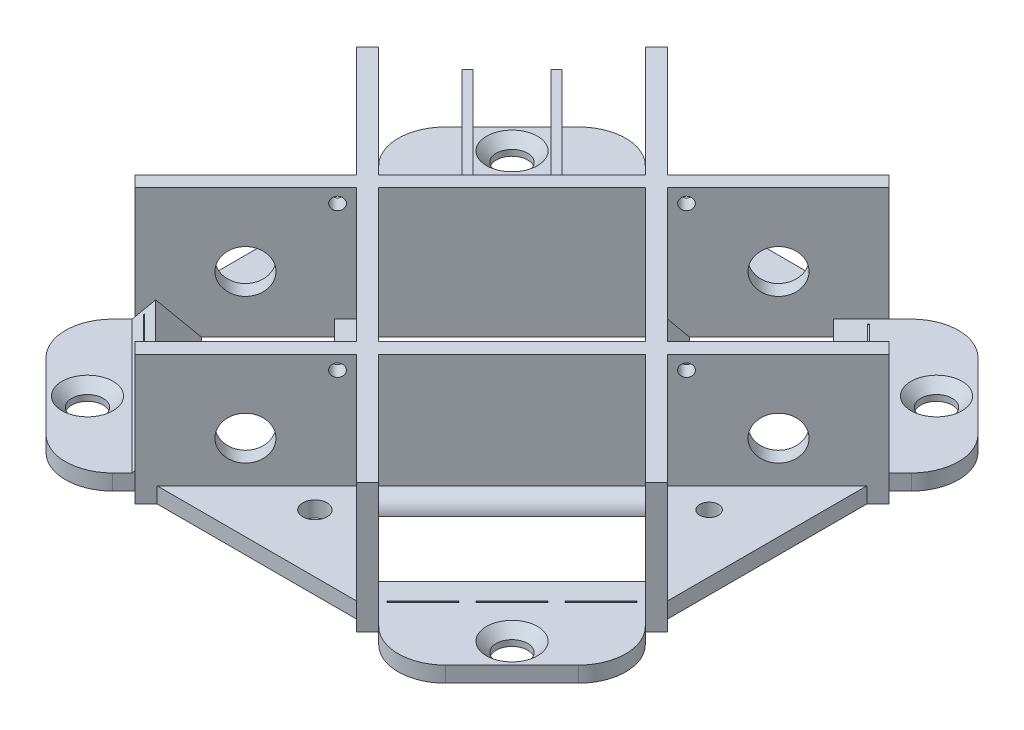
SolidWorks part; units mm, degrees
material "Windform GT"
ref_plane "Front Plane" through (0, 0, 0) normal (0, 0, 1) x (1, 0, 0)
ref_plane "Top Plane" through (0, 0, 0) normal (0, 1, 0) x (1, 0, 0)
ref_plane "Right Plane" through (0, 0, 0) normal (1, 0, 0) x (0, 0, -1)
ref_axis "Axis1" through (0, 2.1, 0) along (0, -1, 0)
sketch "Usable Space" plane through (0, 0, 0) normal (0, 1, 0) x (1, 0, 0)
  line L1 (-32.5, -32.5) -> (32.5, -32.5) construction
  line L2 (-32.5, -32.5) -> (-32.5, 32.5) construction
  line L3 (-32.5, 32.5) -> (32.5, 32.5) construction
  line L4 (32.5, -32.5) -> (32.5, 32.5) construction
  line L5 (-32.5, -32.5) -> (32.5, 32.5) construction
  line L6 (-32.5, 32.5) -> (32.5, -32.5) construction
  point P0 (0, 0)
  dimension "D1" = 65
sketch "Sketch3" plane through (0, 0, 0) normal (0, 1, 0) x (1, 0, 0)
  line L0 (-32.5, -12.701) -> (-12.701, -32.5)
  line L1 (-32.5, -32.5) -> (-32.5, 32.5) construction
  line L2 (-12.701, -32.5) -> (0, -19.799)
  line L3 (-32.5, -32.5) -> (32.5, 32.5) construction
  line L4 (0, -19.799) -> (0, 0)
  line L5 (0, 0) -> (-19.799, 0)
  line L7 (-19.799, 0) -> (-32.5, -12.701)
  line L8 (-32.5, -32.5) -> (32.5, -32.5) construction
  dimension "D1" = 28
extrude "General shape" add sketch "Sketch3" along normal blind 2
sketch "Sketch4" plane through (0, 2, 0) normal (0, 1, 0) x (1, 0, 0)
  line L0 (-19.799, 0) -> (-32.5, -12.701)
  line L1 (-19.799, 0) -> (-32.5, -12.701) construction
  line L2 (-32.5, -12.701) -> (-31.0858, -14.1152)
  line L3 (-31.0858, -14.1152) -> (-16.9706, 0)
  line L4 (0, 0) -> (-19.799, 0) construction
  line L5 (-16.9706, 0) -> (-19.799, 0)
  line L6 (-22.6005, -22.6005) -> (0, 0) construction
  line L7 (-32.5, -12.701) -> (-12.701, -32.5) construction
  line L8 (-14.1152, -31.0858) -> (0, -16.9706)
  line L9 (-12.701, -32.5) -> (-14.1152, -31.0858)
  line L10 (0, -19.799) -> (-12.701, -32.5)
  line L11 (0, -16.9706) -> (0, -19.799)
  dimension "D1" = 2
extrude "Retaining walls" add sketch "Sketch4" along normal blind 14.5
sketch "Sketch14" plane through (0, 0, 0) normal (0, -1, 0) x (1, 0, 0)
  line L0 (-19.799, 0) -> (-32.5, 12.701)
  line L1 (-19.799, 0) -> (-32.5, 12.701) construction
  line L2 (-32.5, 12.701) -> (-32.5, 0)
  line L3 (-32.5, 0) -> (-19.799, 0)
  line L4 (0, 19.799) -> (0, 32.5)
  line L5 (0, 32.5) -> (-12.701, 32.5)
  line L6 (-12.701, 32.5) -> (0, 19.799) construction
  line L7 (0, 19.799) -> (-12.701, 32.5)
  circle A1 centre (-29.049, 0) radius 1 construction
  dimension "D1" = 9.25
  dimension "D2" = 2
extrude "Exterior mounting edge" add sketch "Sketch14" against normal blind 2
sketch "Sketch18" plane through (0, 2, 0) normal (0, 1, 0) x (1, 0, 0)
  line L0 (-16.9706, 0) -> (0, -16.9706)
  line L1 (-18.3848, -1.4142) -> (-1.4142, -18.3848)
  line L2 (-31.0858, -14.1152) -> (-16.9706, 0) construction
  line L3 (0, -16.9706) -> (-14.1152, -31.0858) construction
  line L4 (-18.3848, -1.4142) -> (-16.9706, 0)
  line L5 (0, -16.9706) -> (-1.4142, -18.3848)
  dimension "D1" = 2
extrude "Rear wall" add sketch "Sketch18" along normal blind 14.5
sketch "Sketch19" plane through (-8.4853, 0, 8.4853) normal (0.7071, 0, -0.7071) x (-0.7071, 0, -0.7071)
  line L0 (0, 16.5) -> (0, 2) construction
  line L1 (-12, 16.5) -> (12, 16.5) construction
  line L2 (-12, 2) -> (12, 2) construction
  point P6 (0, 9.25)
fillet "Fillet13" [suppressed] radius 1
ref_plane "Plane2" [suppressed] through (0, 0, 0) normal (0.7071, 0, 0.7071) x (0.7071, 0, -0.7071)
sketch "Sketch35" plane through (-9.8995, 0, -9.8995) normal (-0.7071, 0, -0.7071) x (-0.7071, 0, 0.7071)
  line L0 (24, 16.5) -> (24, 2) construction
  line L2 (14, 16.5) -> (14, 2) construction
  line L3 (14, 2) -> (31.9619, 2) construction
  line L4 (15.7119, 16.5) -> (15.7119, 2) construction
  line L5 (14, 16.5) -> (31.9619, 16.5) construction
  line L6 (14, 2) -> (31.9619, 2) construction
  line L7 (14, 16.5) -> (31.9619, 16.5) construction
  line L8 (31.9619, 16.5) -> (31.9619, 2) construction
  circle A0 centre (24, 7.25) radius 2.75
  circle A1 centre (15.7119, 14.75) radius 0.8
  dimension "D1" = 5.5
  dimension "D4" = 1.6
  dimension "D5" = 1.75
  dimension "D6" = 9.25
  dimension "D2" = 10
  dimension "D3" = 16.25
extrude "Cut-Extrude2" cut sketch "Sketch35" against normal through all both and the other way through all
pattern_circular "CirPattern2" count 4 over 360 about axis through (0, 2.1, 0) along (0, -1, 0) of "General shape", "Retaining walls"
combine bodies "Combine1" operation type add bodies to combine 104 111 110 139
sketch "Exterior mounting hole location" plane through (0, 2, 0) normal (0, 1, 0) x (1, 0, 0)
  line L0 (-32.5, 0) -> (-19.799, 0) construction
  line L1 (-32.5, -12.701) -> (-32.5, 12.701) construction
  point P5 (-25.1, 0)
  point P7 (0, 25.1)
  point P13 (25.1, 0)
  point P14 (0, -25.1)
  dimension "D1" = 4
  dimension "D2" = 25.1
hole_wizard "Exterior mounting hole" positions "Sketch16" profile "Sketch17" hole size "M2" standard "ANSI Metric" end condition up to next
sketch "Sketch16" plane through (0, 2, 0) normal (0, 1, 0) x (1, 0, 0)
  point P0 (-25.1, 0)
  point P15 (25.1, 0)
sketch "Sketch17" plane through (-25.1, 2, 0) normal (1, 0, 0) x (0, 0, 1)
  line L0 (0, 0) -> (0, 2)
  line L1 (0, 2) -> (1.2, 2)
  line L2 (1.2, 2) -> (1.2, 0)
  line L5 (1.2, 0) -> (0, 0)
  line L11 (0, -6.35) -> (0, 107.95) construction
  dimension "Thru Hole Dia." = 2.4
  dimension "Thru Hole Depth" = 2
hole_wizard "Shoulder screw mounting holes " positions "Sketch24" profile "Sketch25" hole size "M2.5" standard "ANSI Metric" end condition up to next
sketch "Sketch24" plane through (0, 2, 0) normal (0, 1, 0) x (1, 0, 0)
  point P0 (0, -25.1)
  point P3 (0, 25.1)
sketch "Sketch25" plane through (0, 2, 25.1) normal (1, 0, 0) x (0, 0, 1)
  line L0 (0, 0) -> (0, 2)
  line L1 (0, 2) -> (1.55, 2)
  line L2 (1.55, 2) -> (1.55, 0)
  line L5 (1.55, 0) -> (0, 0)
  line L11 (0, -6.35) -> (0, 107.95) construction
  dimension "Thru Hole Dia." = 3.1
  dimension "Thru Hole Depth" = 2
sketch "Sketch23" plane through (0, 2, 0) normal (0, 1, 0) x (1, 0, 0)
  line L0 (0, 16.9706) -> (-16.9706, 0)
  line L5 (-16.9706, 0) -> (0, -16.9706)
  line L6 (0, -16.9706) -> (16.9706, 0)
  line L7 (16.9706, 0) -> (0, 16.9706)
  line L8 (31.0858, 14.1152) -> (18.3848, 1.4142) construction
  line L9 (18.3848, 1.4142) -> (1.4142, 18.3848) construction
  line L10 (1.4142, 18.3848) -> (14.1152, 31.0858) construction
  line L11 (-18.3848, 1.4142) -> (-31.0858, 14.1152) construction
  line L12 (-1.4142, 18.3848) -> (-18.3848, 1.4142) construction
  line L13 (-14.1152, 31.0858) -> (-1.4142, 18.3848) construction
  line L14 (-1.4142, -18.3848) -> (-14.1152, -31.0858) construction
  line L15 (-18.3848, -1.4142) -> (-1.4142, -18.3848) construction
  line L16 (-31.0858, -14.1152) -> (-18.3848, -1.4142) construction
  line L17 (14.1152, -31.0858) -> (1.4142, -18.3848) construction
  line L18 (18.3848, -1.4142) -> (31.0858, -14.1152) construction
  line L19 (1.4142, -18.3848) -> (18.3848, -1.4142) construction
  line L20 (31.0858, 14.1152) -> (18.3848, 1.4142)
  line L21 (18.3848, 1.4142) -> (1.4142, 18.3848)
  line L22 (1.4142, 18.3848) -> (14.1152, 31.0858)
  line L23 (-18.3848, 1.4142) -> (-31.0858, 14.1152)
  line L24 (-1.4142, 18.3848) -> (-18.3848, 1.4142)
  line L25 (-14.1152, 31.0858) -> (-1.4142, 18.3848)
  line L26 (-1.4142, -18.3848) -> (-14.1152, -31.0858)
  line L27 (-18.3848, -1.4142) -> (-1.4142, -18.3848)
  line L28 (-31.0858, -14.1152) -> (-18.3848, -1.4142)
  line L29 (14.1152, -31.0858) -> (1.4142, -18.3848)
  line L30 (18.3848, -1.4142) -> (31.0858, -14.1152)
  line L31 (1.4142, -18.3848) -> (18.3848, -1.4142)
  line L32 (-14.1152, 31.0858) -> (-31.0858, 14.1152)
  line L33 (-14.1152, -31.0858) -> (-31.0858, -14.1152)
  line L34 (14.1152, -31.0858) -> (31.0858, -14.1152)
  line L35 (31.0858, 14.1152) -> (14.1152, 31.0858)
extrude "Cut-Extrude1" cut sketch "Sketch23" against normal up to next
sketch "Sketch36" plane through (0, 0, 0) normal (0, 1, 0) x (1, 0, 0)
  line L6 (-12.701, -32.5) -> (-15.5294, -32.5)
  line L7 (-15.5294, -32.5) -> (-21.1863, -38.1569)
  line L8 (-21.1863, -38.1569) -> (-38.1569, -21.1863)
  line L16 (-38.1569, -21.1863) -> (-32.5, -15.5294)
  line L17 (-32.5, -12.701) -> (-31.0858, -14.1152)
  line L18 (-32.5, -15.5294) -> (-32.5, -12.701)
  line L19 (-32.5, -12.701) -> (-32.5, 12.701) construction
  line L20 (12.701, -32.5) -> (-12.701, -32.5) construction
  line L22 (-1.4142, -18.3848) -> (-14.1152, -31.0858) construction
  line L23 (-31.0858, -14.1152) -> (-18.3848, -1.4142) construction
  line L24 (-31.0858, -14.1152) -> (-29.6716, -12.701)
  line L25 (-12.701, -29.6716) -> (-14.1152, -31.0858)
  line L26 (-29.6716, -12.701) -> (-12.701, -29.6716)
  line L27 (-14.1152, -31.0858) -> (-12.701, -32.5)
  line L28 (-18.3848, -1.4142) -> (-1.4142, -18.3848) construction
  line L29 (-1.4142, -18.3848) -> (-2.8284, -19.799)
  line L30 (-18.3848, -1.4142) -> (-1.4142, -18.3848)
  line L31 (-31.0858, -14.1152) -> (-29.6716, -12.701)
  line L32 (-19.799, -2.8284) -> (-2.8284, -19.799)
  line L33 (-19.799, -2.8284) -> (-18.3848, -1.4142)
  line L34 (-12.701, -29.6716) -> (-14.1152, -31.0858)
  dimension "D1" = 10
  dimension "D2" = 2
  dimension "D3" = 2
extrude "Boss-Extrude2" add sketch "Sketch36" along normal up to surface (2 mm away) contours L27 L25 L26 L24 L17 L18 L16 L8 L7 L6 | L32 L29 L30 L33 region at (-25.3966, 0, 25.3966)
sketch "Sketch37" plane through (-8.4853, 0, -8.4853) normal (0.7071, 0, 0.7071) x (0.7071, 0, -0.7071)
  line L0 (-32.0833, 4.1213) -> (-29.9619, 2)
  line L1 (-34.2046, 2) -> (-29.9619, 2)
  line L2 (-29.9619, 2) -> (-27.9619, 0)
  line L4 (-33.9619, 2) -> (-41.9619, 2) construction
  line L5 (-32.0833, 4.1213) -> (-34.2046, 2)
  line L6 (-27.9619, 0) -> (-29.9619, 0)
  line L7 (-29.9619, 0) -> (-29.9619, 2)
  line L8 (-14, 0) -> (-33.9619, 0) construction
  line M17 (-31.9619, 16.5) -> (-31.9619, 2)
  line M18 (-31.9619, 2) -> (-29.9619, 2)
  line M19 (-29.9619, 2) -> (-29.9619, 0)
  line M20 (-29.9619, 0) -> (-16, 0)
  dimension "D2" = 45
  dimension "D3" = 3
extrude "Boss-Extrude3" add sketch "Sketch37" along normal up to surface (24 mm away) contours L0 L5 L1 | L0 M17 M18 | L2 M19 M20 region at (-29.2002, 0.6667, 12.2296) region at (-31.6173, 2.7395, 14.6468) region at (-30.6144, 2.6667, 13.6438) up to face at (-6.5407, 7.25, 23.5113)
sketch "Sketch40" plane through (-12.8003, 18.1023, 12.8003) normal (-0.5, 0.7071, 0.5) x (0.866, 0.4082, 0.2887)
  line L0 (-21.4295, -10.8203) -> (-3.0583, -23.8107)
  line L1 (-3.0583, -23.8107) -> (-3.1334, -23.9168)
  line L2 (-3.1334, -23.9168) -> (-21.5046, -10.9265)
  line L3 (-21.5046, -10.9265) -> (-21.4295, -10.8203)
  line L5 (-3.3495, -25.5215) -> (-22.9454, -11.6651) construction
  line L7 (-1.6175, -23.072) -> (-3.3495, -25.5215) construction
  line L8 (-22.0794, -10.4404) -> (-2.4835, -24.2968) construction
  line L9 (-1.6175, -23.072) -> (-3.3495, -25.5215) construction
  line L10 (-16.1223, -14.5731) -> (-16.1973, -14.6792)
  line L11 (-14.8975, -15.4391) -> (-14.9726, -15.5453)
  line L12 (-8.3656, -20.0579) -> (-8.4406, -20.1641)
  line L13 (-9.5903, -19.1919) -> (-9.6654, -19.298)
  line L16 (-1.6175, -23.072) -> (-21.2134, -9.2156) construction
  line L18 (-11.4154, -16.1438) -> (-13.1475, -18.5933) construction
  line L20 (-3.3495, -25.5215) -> (-22.9454, -11.6651) construction
  point P18 (-2.4835, -24.2968)
  point P33 (-13.1475, -18.5933)
  point P45 (-11.4154, -16.1438)
  dimension "D1" = 0.065
  dimension "D2" = 0.065
  dimension "D3" = 6.5
  dimension "D4" = 1.5
  dimension "D5" = 1.5
  dimension "D6" = 6.5
  dimension "D7" = 3.25
  dimension "D8" = 6.5
extrude "Cut-Extrude3" cut sketch "Sketch40" against normal up to surface (4.3934 mm away) contours L0 L12 L2 L1 | L13 L0 L11 L2 | L10 L0 L3 L2 region at (-29.0931, 3.0607, 17.7794) region at (-23.4363, 3.0607, 23.4363) region at (-17.7794, 3.0607, 29.0931) up to face at (-15.5429, 0, 15.5429)
sketch "Sketch41" plane through (0, 2, 0) normal (0, 1, 0) x (1, 0, 0)
  line L13 (-12.701, -32.5) -> (-15.5294, -32.5) construction
  line L14 (-14.1152, -31.0858) -> (-12.701, -32.5) construction
  line L15 (-12.701, -32.5) -> (-15.5294, -32.5)
  line L16 (-14.1152, -31.0858) -> (-12.701, -32.5)
  line L17 (-32.5, -12.701) -> (-31.0858, -14.1152) construction
  line L18 (-32.5, -15.5294) -> (-32.5, -12.701) construction
  line L19 (-32.5, -12.701) -> (-31.0858, -14.1152)
  line L20 (-32.5, -15.5294) -> (-32.5, -12.701)
  line L21 (-31.0858, -14.1152) -> (-32.5, -15.5294)
  line L23 (-15.5294, -32.5) -> (-14.1152, -31.0858)
extrude "Boss-Extrude4" add sketch "Sketch41" along normal up to surface (14.5 mm away) up to face at (0, 16.5, 0)
fillet "Fillet14" radius 6 2 edges at (-38.1569, 1, 21.1863) (-21.1863, 1, 38.1569)
sketch "Sketch42" plane through (0, 2, 0) normal (0, 1, 0) x (1, 0, 0)
  circle A1 centre (-27.0307, -27.0307) radius 2.653 construction
  circle A2 centre (-27.0307, -27.0307) radius 2.653 construction
  circle A3 centre (-27.0307, -27.0307) radius 2
  dimension "D1" = 4
extrude "Cut-Extrude4" cut sketch "Sketch42" against normal through all
chamfer "Chamfer1" distance 1.25 angle 45 1 edges at (-27.0307, 2, 29.0307)
pattern_circular "CirPattern15" count 4 over 360 about axis through (0, 2.1, 0) along (0, -1, 0) of "Boss-Extrude2", "Cut-Extrude3", "Fillet14", "Cut-Extrude4", "Boss-Extrude4", "Chamfer1"
sketch "Sketch43" plane through (0, 0, 0) normal (0, 1, 0) x (1, 0, 0)
  line L0 (-12.701, 29.6716) -> (-29.6716, 12.701) construction
  line L1 (-12.701, 29.6716) -> (-29.6716, 12.701)
  line L2 (29.6716, 12.701) -> (12.701, 29.6716) construction
  line L3 (12.701, -29.6716) -> (29.6716, -12.701) construction
  line L4 (29.6716, 12.701) -> (12.701, 29.6716)
  line L5 (12.701, -29.6716) -> (29.6716, -12.701)
  line L6 (-11.9939, 28.9645) -> (-28.9645, 11.9939)
  line L7 (28.9645, 11.9939) -> (11.9939, 28.9645)
  line L8 (11.9939, -28.9645) -> (28.9645, -11.9939)
  line L9 (-12.701, 29.6716) -> (-11.9939, 28.9645)
  line L10 (-29.6716, 12.701) -> (-28.9645, 11.9939)
  line L11 (11.9939, 28.9645) -> (12.701, 29.6716)
  line L12 (29.6716, 12.701) -> (28.9645, 11.9939)
  line L13 (28.9645, -11.9939) -> (29.6716, -12.701)
  line L14 (11.9939, -28.9645) -> (12.701, -29.6716)
  point P0 (0, 0)
  point P2 (0, 0)
  point P8 (0, 0)
  point P11 (0, 0)
  point P16 (0, 0)
  point P17 (0, 0)
  point P21 (0, 0)
  point P22 (0, 0)
  point P23 (0, 0)
  point P24 (0, 0)
  dimension "D1" = 1
extrude "Boss-Extrude5" add sketch "Sketch43" along normal up to surface (2 mm away) up to face at (-27.0307, 2, -23.7807)
sketch "Sketch44" plane through (0, 0, 0) normal (0, 1, 0) x (1, 0, 0)
  line L0 (-32.5, 15.5294) -> (-32.5, 12.701) construction
  line L1 (-12.701, 32.5) -> (-15.5294, 32.5) construction
  line L2 (15.5294, 32.5) -> (12.701, 32.5) construction
  line L3 (32.5, 12.701) -> (32.5, 15.5294) construction
  line L4 (32.5, -15.5294) -> (32.5, -12.701) construction
  line L5 (-15.5294, -32.5) -> (-12.701, -32.5) construction
  line L6 (-32.5, 15.5294) -> (-32.5, 12.701)
  line L7 (-12.701, 32.5) -> (-15.5294, 32.5)
  line L8 (15.5294, 32.5) -> (12.701, 32.5)
  line L9 (32.5, 12.701) -> (32.5, 15.5294)
  line L10 (32.5, -15.5294) -> (32.5, -12.701)
  line L11 (-15.5294, -32.5) -> (-12.701, -32.5)
  line L12 (-32.5, 15.5294) -> (-33.9142, 14.1152)
  line L13 (-33.9142, 14.1152) -> (-32.5, 12.701)
  line L14 (-32.5, -12.701) -> (-32.5, -15.5294) construction
  line L15 (-32.5, -12.701) -> (-32.5, -15.5294)
  line L16 (-32.5, -12.701) -> (-33.9142, -14.1152)
  line L17 (-33.9142, -14.1152) -> (-32.5, -15.5294)
  line L18 (-15.5294, -32.5) -> (-14.1152, -33.9142)
  line L19 (-14.1152, -33.9142) -> (-12.701, -32.5)
  line L20 (12.701, -32.5) -> (15.5294, -32.5) construction
  line L21 (12.701, -32.5) -> (15.5294, -32.5)
  line L22 (12.701, -32.5) -> (14.1152, -33.9142)
  line L23 (14.1152, -33.9142) -> (15.5294, -32.5)
  line L24 (32.5, -15.5294) -> (33.9142, -14.1152)
  line L25 (33.9142, -14.1152) -> (32.5, -12.701)
  line L26 (32.5, 12.701) -> (33.9142, 14.1152)
  line L27 (33.9142, 14.1152) -> (32.5, 15.5294)
  line L28 (15.5294, 32.5) -> (14.1152, 33.9142)
  line L29 (14.1152, 33.9142) -> (12.701, 32.5)
  line L30 (-12.701, 32.5) -> (-14.1152, 33.9142)
  line L31 (-14.1152, 33.9142) -> (-15.5294, 32.5)
  line L32 (-12.701, -32.5) -> (0, -19.799) construction
  point P1 (0, 0)
  point P6 (0, 0)
  point P8 (0, 0)
  point P10 (0, 0)
  point P11 (0, 0)
  point P12 (-33.2071, 14.8223)
  point P16 (0, 0)
  point P17 (0, 0)
  point P24 (0, 0)
  point P25 (0, 0)
  point P30 (0, 0)
  point P34 (0, 0)
  point P36 (0, 0)
  point P37 (0, 0)
  point P39 (0, 0)
  point P40 (0, 0)
  point P41 (40.9541, 15.9213)
  point P42 (0, 0)
  point P43 (0, 0)
  point P44 (0, 0)
  point P45 (-36.4463, 12.6603)
  point P46 (-35.4872, 15.8254)
  point P47 (0, 0)
  point P48 (33.2071, 13.4081)
  point P49 (-14.1152, -34.0495)
  point P52 (14.1152, -33.9142)
  point P53 (34.2247, 15.6117)
  point P54 (0, 0)
extrude "Boss-Extrude6" add sketch "Sketch44" along normal up to surface (16.5 mm away) up to face at (0, 16.5, 0)
sketch "Sketch45" plane through (0, 0, 0) normal (0, 1, 0) x (1, 0, 0)
  line L1 (-21.5398, 26.4896) -> (-7.4246, 12.3744)
  line L2 (-20.8327, 27.1967) -> (-6.7175, 13.0815)
  line L3 (-20.8327, 27.1967) -> (-6.7175, 13.0815)
  line L5 (-21.5398, 26.4896) -> (-20.8327, 27.1967)
  line L6 (-6.7175, 13.0815) -> (-7.4246, 12.3744)
  line L7 (0, 0) -> (-29.6716, 29.6716) construction
  line L8 (-15.5294, 32.5) -> (-1.4142, 18.3848) construction
  line L9 (-33.9142, 25.4289) -> (-25.4289, 33.9142) construction
  line L10 (-13.0815, 6.7175) -> (-12.3744, 7.4246)
  line L11 (-26.4896, 21.5398) -> (-27.1967, 20.8327)
  line L12 (-27.1967, 20.8327) -> (-13.0815, 6.7175)
  line L13 (-26.4896, 21.5398) -> (-12.3744, 7.4246)
  point P0 (0, 0)
  point P4 (0, 0)
  point P10 (0, 0)
  point P14 (0, 0)
  point P17 (0, 0)
  dimension "D1" = 7.5
  dimension "D2" = 1
extrude "Boss-Extrude7" add sketch "Sketch45" along normal offset from surface (14 mm away) 2.5 up to face at (0, 16.5, 0)
sketch "Sketch46" plane through (9.8995, 0, -9.8995) normal (0.7071, 0, -0.7071) x (-0.7071, 0, -0.7071)
  circle A0 centre (24, 7.25) radius 2.75 construction
  circle A1 centre (24, 7.25) radius 2.75
extrude "Cut-Extrude5" cut sketch "Sketch46" against normal through all both and the other way through all
fillet "Fillet15" radius 2 1 edges at (11.3137, 2, 11.3137)
chamfer "Chamfer2" distance 2 angle 45 1 edges at (11.3137, 2, -11.3137)
